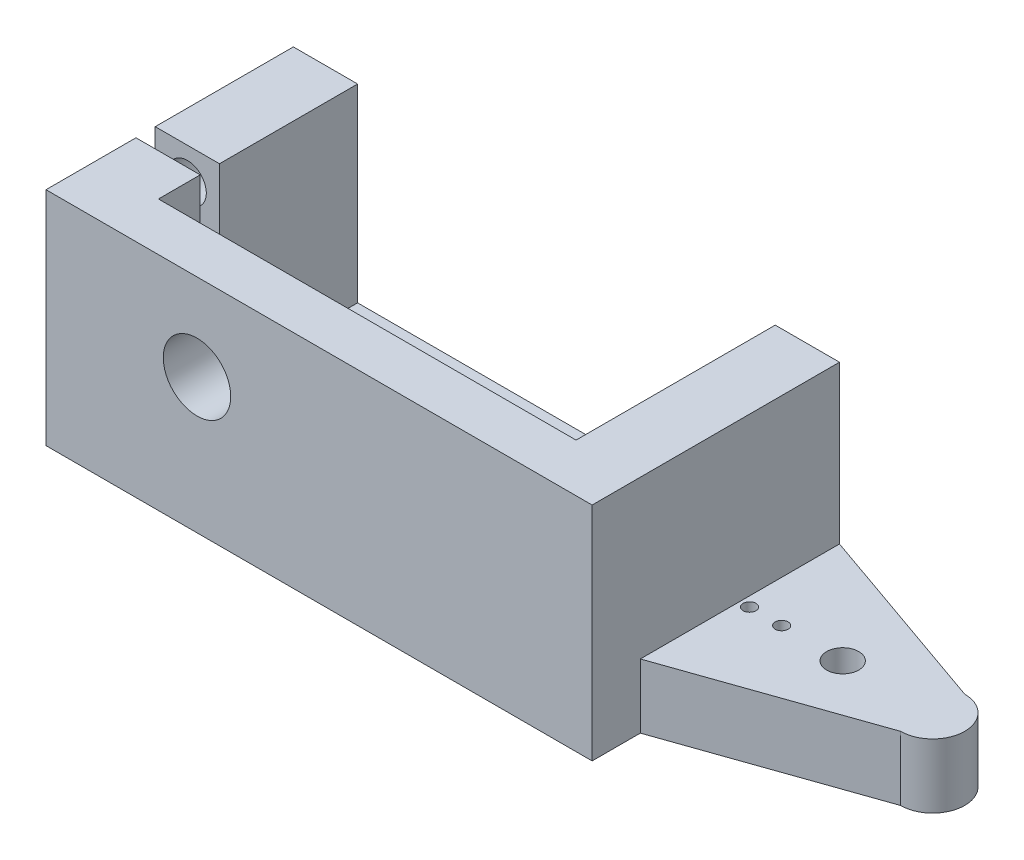
SolidWorks part; units mm, degrees
ref_plane "Front Plane" through (0, 0, 0) normal (0, 0, 1) x (1, 0, 0)
ref_plane "Top Plane" through (0, 0, 0) normal (0, 1, 0) x (1, 0, 0)
ref_plane "Right Plane" through (0, 0, 0) normal (1, 0, 0) x (0, 0, -1)
sketch "Sketch1" plane through (0, 0, 0) normal (0, 0, 1) x (1, 0, 0)
  line L1 (-37.5, -8.5) -> (37.5, -8.5) construction
  line L2 (-37.5, -8.5) -> (-37.5, 8.5) construction
  line L3 (-37.5, 8.5) -> (37.5, 8.5) construction
  line L4 (37.5, -8.5) -> (37.5, 8.5) construction
  line L5 (-37.5, -8.5) -> (37.5, 8.5) construction
  line L6 (-37.5, 8.5) -> (37.5, -8.5) construction
  line L7 (-42.5, 13.5) -> (-32.5, 13.5)
  line L8 (-42.5, 13.5) -> (-42.5, -16)
  line L9 (-42.5, -16) -> (-32.5, -16)
  line L10 (-32.5, 13.5) -> (-32.5, -16)
  line L11 (32.5, 13.5) -> (42.5, 13.5)
  line L12 (32.5, 13.5) -> (32.5, -16)
  line L13 (32.5, -16) -> (42.5, -16)
  line L14 (42.5, 13.5) -> (42.5, -16)
  line L19 (-42.5, -16) -> (42.5, -16)
  line L20 (-42.5, -16) -> (-42.5, -21)
  line L21 (-42.5, -21) -> (42.5, -21)
  line L22 (42.5, -16) -> (42.5, -21)
  circle A0 centre (-37.5, 8.5) radius 2.95
  circle A1 centre (37.5, 8.5) radius 2.95
  circle A2 centre (-37.5, -8.5) radius 2.95
  circle A3 centre (37.5, -8.5) radius 2.95
  point P8 (0, 0)
  point P23 (-37.5, 13.5)
  point P25 (37.5, 13.5)
  dimension "D1" = 5.9
  dimension "D2" = 75
  dimension "D3" = 17
  dimension "D4" = 10
  dimension "D5" = 5
  dimension "D6" = 7.5
  dimension "D7" = 5
extrude "Boss-Extrude1" add sketch "Sketch1" along normal mid plane 31 contours L14 L11 L12 L13 A3 A1 | L13 L9 | L10 L7 L8 L9 A2 A0 region at (-37.5, -1.5344, 0) region at (0, -18.5, 0) region at (37.5, -1.5344, 0)
sketch "Sketch2" plane through (0, -21, 0) normal (0, -1, 0) x (1, 0, 0)
  line L0 (42.5, 15.5) -> (72.5, 5)
  line L1 (42.5, -15.5) -> (72.5, -5)
  line L2 (42.5, 0) -> (72.5, 0) construction
  line L4 (42.5, 15.5) -> (42.5, -15.5)
  line L5 (42.5, 15.5) -> (42.5, -15.5) construction
  line L6 (-42.5, 15.5) -> (42.5, 15.5) construction
  arc A0 (72.5, -5) -> (72.5, 5) centre (72.5, 0) ccw
  dimension "D2" = 5
  dimension "D1" = 30
extrude "Boss-Extrude2" add sketch "Sketch2" against normal blind 10 contours L1 A0 L0 L4 region at (56.1204, -21, 0)
sketch "Sketch3" plane through (0, -21, 0) normal (0, -1, 0) x (1, 0, 0)
  line L0 (18.975, 0) -> (-18.975, 0) construction
  line L1 (42.5, 15.5) -> (42.5, -15.5) construction
  line L2 (-42.5, -15.5) -> (42.5, -15.5) construction
  circle A0 centre (58.5, 0) radius 2.5
  circle A1 centre (49, 0) radius 1
  circle A2 centre (44, 0) radius 1
  dimension "D1" = 5
  dimension "D2" = 2
  dimension "D3" = 5
  dimension "D4" = 9.5
  dimension "D5" = 16
extrude "Cut-Extrude1" cut sketch "Sketch3" against normal blind 10
sketch "Sketch4" plane through (0, 0, 15.5) normal (0, 0, 1) x (1, 0, 0)
  line L1 (-42.5, -21) -> (42.5, -21)
  line L2 (-42.5, -21) -> (-42.5, 13.5)
  line L3 (-42.5, 13.5) -> (42.5, 13.5)
  line L4 (42.5, -21) -> (42.5, 13.5)
  circle A0 centre (-19, 0) radius 1.6 construction
  circle A1 centre (-19, 0) radius 1.6 construction
  circle A2 centre (-19, 0) radius 5.25
  dimension "D1" = 10.5
extrude "Boss-Extrude3" add sketch "Sketch4" along normal blind 7.5
sketch "Sketch5" plane through (0, -21, 0) normal (0, -1, 0) x (1, 0, 0)
  line L2 (17.4294, -2.7313) -> (57.6258, -7.4489)
  line L3 (57.6258, 7.4489) -> (17.4294, 2.7313)
  line L4 (17.4294, -2.7313) -> (57.6258, -7.4489)
  line L5 (57.6258, 7.4489) -> (17.4294, 2.7313)
  circle A0 centre (58.5, 0) radius 5.65 construction
  circle A1 centre (58.5, 0) radius 5.65
  arc A2 (57.6258, -7.4489) -> (57.6258, 7.4489) centre (58.5, 0) ccw
  arc A3 (17.4294, 2.7313) -> (17.4294, -2.7313) centre (17.75, 0) ccw
  arc A4 (57.6258, -7.4489) -> (57.6258, 7.4489) centre (58.5, 0) ccw
  arc A5 (17.4294, 2.7313) -> (17.4294, -2.7313) centre (17.75, 0) ccw
  circle M5 centre (58.5, 0) radius 2.5
  dimension "D1" = 0
extrude "Cut-Extrude2" cut sketch "Sketch5" against normal blind 3 contours A1 M5 region at (53.0098, -21, 0)
sketch "Sketch6" plane through (0, -21, 0) normal (0, -1, 0) x (1, 0, 0)
  line L2 (17.4294, -2.7313) -> (57.6258, -7.4489)
  line L3 (57.6258, 7.4489) -> (17.4294, 2.7313)
  line L4 (17.4294, -2.7313) -> (57.6258, -7.4489)
  line L5 (57.6258, 7.4489) -> (17.4294, 2.7313)
  circle A1 centre (58.5, 0) radius 5.65
  circle A2 centre (58.5, 0) radius 5.65
  arc A4 (57.6258, -7.4489) -> (57.6258, 7.4489) centre (58.5, 0) ccw
  arc A5 (17.4294, 2.7313) -> (17.4294, -2.7313) centre (17.75, 0) ccw
  arc A6 (57.6258, -7.4489) -> (57.6258, 7.4489) centre (58.5, 0) ccw
  arc A7 (17.4294, 2.7313) -> (17.4294, -2.7313) centre (17.75, 0) ccw
  dimension "D1" = 0
  dimension "D2" = 0
extrude "Cut-Extrude3" cut sketch "Sketch6" against normal blind 2
sketch "Sketch7" plane through (-42.5, 0, 0) normal (-1, 0, 0) x (0, 0, 1)
  line L0 (23, 13.5) -> (23, -21) construction
  line L1 (6, -6.5) -> (9, -6.5)
  line L2 (6, -6.5) -> (6, 13.5)
  line L3 (6, 13.5) -> (9, 13.5)
  line L4 (9, -6.5) -> (9, 13.5)
  line L5 (6, -6.5) -> (9, 13.5) construction
  line L6 (6, 13.5) -> (9, -6.5) construction
  line L7 (23, 13.5) -> (-15.5, 13.5) construction
  point P0 (7.5, 3.5)
  dimension "D1" = 3
  dimension "D2" = 14
  dimension "D3" = 20
extrude "Cut-Extrude4" cut sketch "Sketch7" against normal up to surface (10 mm away) up to face at (-32.5, -1.25, 0)
